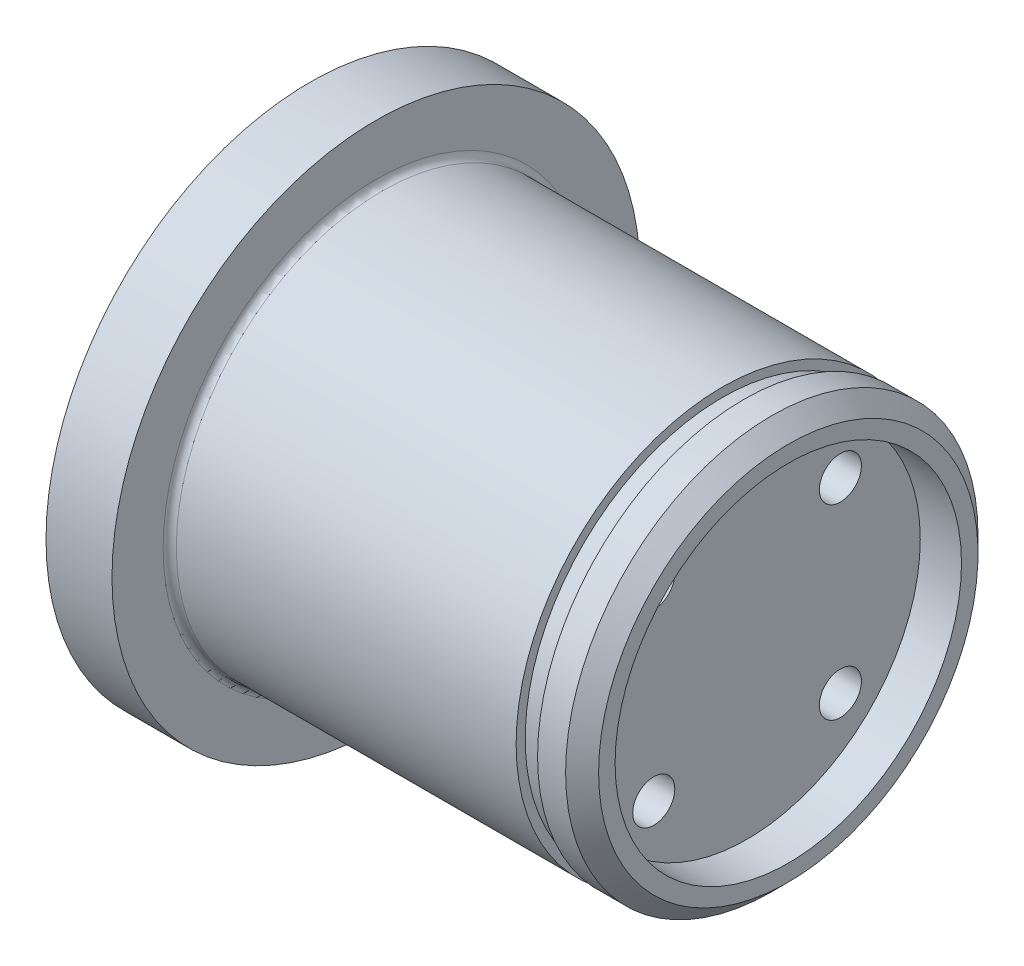
SolidWorks part; units mm, degrees
material "1060 Сплав"
ref_plane "Спереди" through (0, 0, 0) normal (0, 0, 1) x (1, 0, 0)
ref_plane "Сверху" through (0, 0, 0) normal (0, 1, 0) x (1, 0, 0)
ref_plane "Справа" through (0, 0, 0) normal (1, 0, 0) x (0, 0, -1)
sketch "Эскиз1" plane through (0, 0, 0) normal (0, 0, 1) x (1, 0, 0)
  line L0 (0, 0) -> (22138.4448, 0) construction
  line L1 (0, 0) -> (0, 12.5)
  line L2 (0, 12.5) -> (-25, 12.5)
  line L3 (-25, 12.5) -> (-25, 16)
  line L4 (-25, 16) -> (-29, 16)
  line L5 (-29, 16) -> (-29, 0)
  line L8 (0, 0) -> (-29, 0)
  dimension "D1" = 29
  dimension "D2" = 4
  dimension "D3" = 25
  dimension "D6" = 32
revolve "Повернуть1" add sketch "Эскиз1" angle 360 about L0
sketch "Эскиз2" plane through (0, 0, 0) normal (0, 0, 1) x (1, 0, 0)
  line L0 (-4, 12.5) -> (-4, 11.95)
  line L1 (-4, 12.5) -> (-24.6, 12.5) construction
  line L2 (-4, 11.95) -> (-2.7, 11.95)
  line L3 (-2.7, 11.95) -> (-2.7, 12.5)
  line L4 (-2.7, 12.5) -> (-4, 12.5)
  line L5 (0, -12.5) -> (0, 12.5) construction
  line L6 (0, 0) -> (-50000, 0) construction
  point P10 (-2.7, 12.225)
  point P13 (0, 0)
  dimension "D1" = 4
  dimension "D2" = 1.3
  dimension "D3" = 23.9
revolve "Вырез-Повернуть1" cut sketch "Эскиз2" angle 360 about L6
chamfer "Фаска1" distance 1 angle 45 1 edges at (0, 0, 12.5)
fillet "Скругление1" radius 0.4 1 edges at (-25, 0, 12.5)
hole_wizard "Сверло под метчик  спиральное M2.51" positions "Эскиз3" profile "Эскиз4" hole size "M2.5x0.45" standard "Ansi Metric" end condition through all
sketch "Эскиз3" plane through (0, 0, 0) normal (1, 0, 0) x (0, 0, -1)
  line L0 (0, 0) -> (0, 8) construction
  line L2 (0, 0) -> (5.6569, 5.6569) construction
  circle A0 centre (0, 0) radius 8 construction
  point P0 (5.6569, 5.6569)
  dimension "D1" = 16
  dimension "D2" = 45
sketch "Эскиз4" plane through (0, 5.6569, -5.6569) normal (0, 1, 0) x (0, 0, -1)
  line L0 (0, 0) -> (0, 29)
  line L1 (0, 29) -> (1.275, 29)
  line L2 (1.275, 29) -> (1.275, 0)
  line L5 (1.275, 0) -> (0, 0)
  line L11 (0, -6.35) -> (0, 107.95) construction
  dimension "Диаметр сквозного отверстия" = 2.55
  dimension "Глубина сквозного отверстия" = 29
pattern_circular "Круговой массив1" count 4 over 360 about axis through (0, 0, 0) along (-1, 0, 0) of "Сверло под метчик  спиральное M2.51"
sketch "Эскиз5" plane through (0, 0, 0) normal (0, 0, 1) x (1, 0, 0)
  line L0 (0, 0) -> (0, 10.5)
  line L1 (0, -11.5) -> (0, 11.5) construction
  line L7 (0, 10.5) -> (-2.5, 10.5)
  line L8 (-2.5, 10.5) -> (-2.5, 0)
  line L9 (-2.5, 0) -> (0, 0)
  line L10 (0, 0) -> (-50000, 0) construction
  dimension "D1" = 2.5
  dimension "D2" = 21
revolve "Вырез-Повернуть2" cut sketch "Эскиз5" angle 360 about L10
